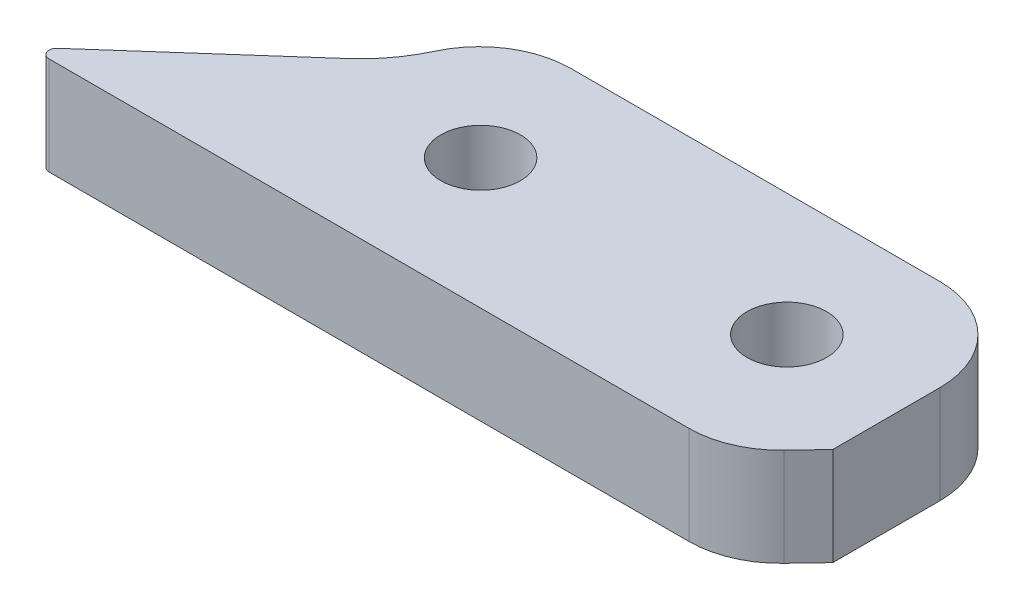
SolidWorks part; units mm, degrees
material "Titanium Ti-8Mn, Annealed"
ref_plane "Front Plane" through (0, 0, 0) normal (0, 0, 1) x (1, 0, 0)
ref_plane "Top Plane" through (0, 0, 0) normal (0, 1, 0) x (1, 0, 0)
ref_plane "Right Plane" through (0, 0, 0) normal (1, 0, 0) x (0, 0, -1)
sketch "Sketch1" plane through (0, 0, 0) normal (0, 1, 0) x (1, 0, 0)
  line L5 (36, -13) -> (36, 0)
  line L6 (36, 0) -> (0, 0)
  line L8 (36, -13) -> (32.6676, -16.5)
  line L9 (32.6676, -16.5) -> (-1.4555, -16.5)
  line L10 (0, 0) -> (0, -5)
  line L11 (0, -5) -> (-13, -16.5)
  line L12 (-13, -16.5) -> (-1.4555, -16.5)
  circle A0 centre (28, -8) radius 2.6
  circle A1 centre (8, -8) radius 2.6
  dimension "D8" = 5.2
  dimension "D9" = 5.2
  dimension "D1" = 13
  dimension "D2" = 36
  dimension "D3" = 8
  dimension "D4" = 13
  dimension "D5" = 5
  dimension "D6" = 8.5
  dimension "D10" = 20
  dimension "D11" = 8
extrude "Boss-Extrude1" add sketch "Sketch1" along normal blind 6.4
fillet "Fillet1" radius 6 3 edges at (32.6676, 3.2, 16.5) (36, 3.2, 0) (0, 3.2, 0)
fillet "Fillet2" radius 10 1 edges at (0, 3.2, 5)
fillet "Fillet3" radius 0.5 1 edges at (-13, 3.2, 16.5)
